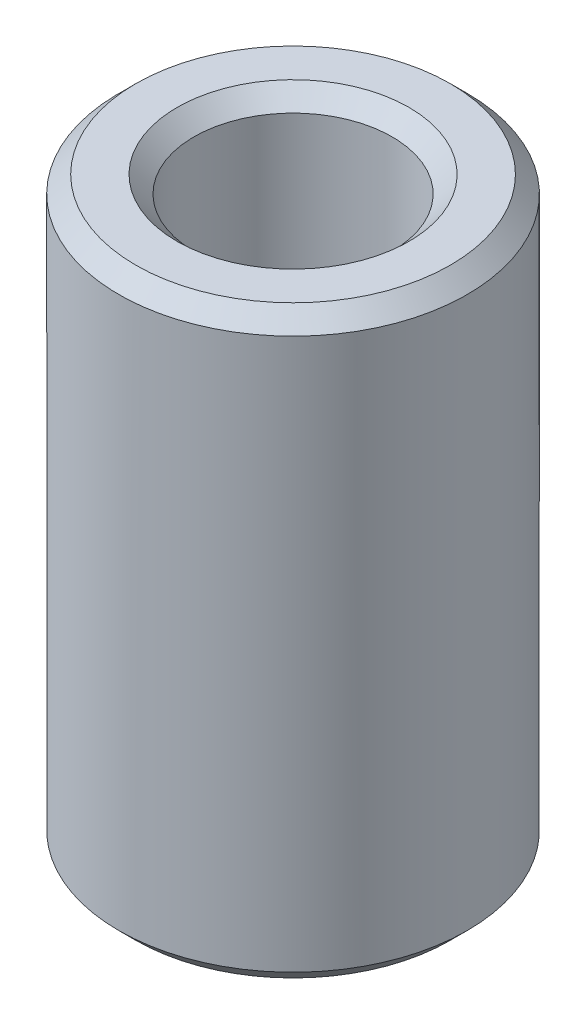
SolidWorks part; units mm, degrees
ref_plane "Front Plane" through (0, 0, 0) normal (0, 0, 1) x (1, 0, 0)
ref_plane "Top Plane" through (0, 0, 0) normal (0, 1, 0) x (1, 0, 0)
ref_plane "Right Plane" through (0, 0, 0) normal (1, 0, 0) x (0, 0, -1)
sketch "Sketch1" plane through (0, 0, 0) normal (0, 1, 0) x (1, 0, 0)
  circle A0 centre (0, 0) radius 40
  dimension "SLEEVE_OD" = 80
extrude "Boss-Extrude1" add sketch "Sketch1" along normal blind 134.2673
sketch "Sketch2" plane through (0, 0, 0) normal (0, 1, 0) x (1, 0, 0)
  circle A0 centre (0, 0) radius 22.7492
  dimension "BORE_D" = 45.4984
extrude "Cut-Extrude1" cut sketch "Sketch2" along normal through all
chamfer "Chamfer1" distance 3.8918 angle 45 4 edges at (0, 134.2673, 22.7492) (0, 0, 22.7492) (0, 0, 40) (0, 134.2673, 40)
